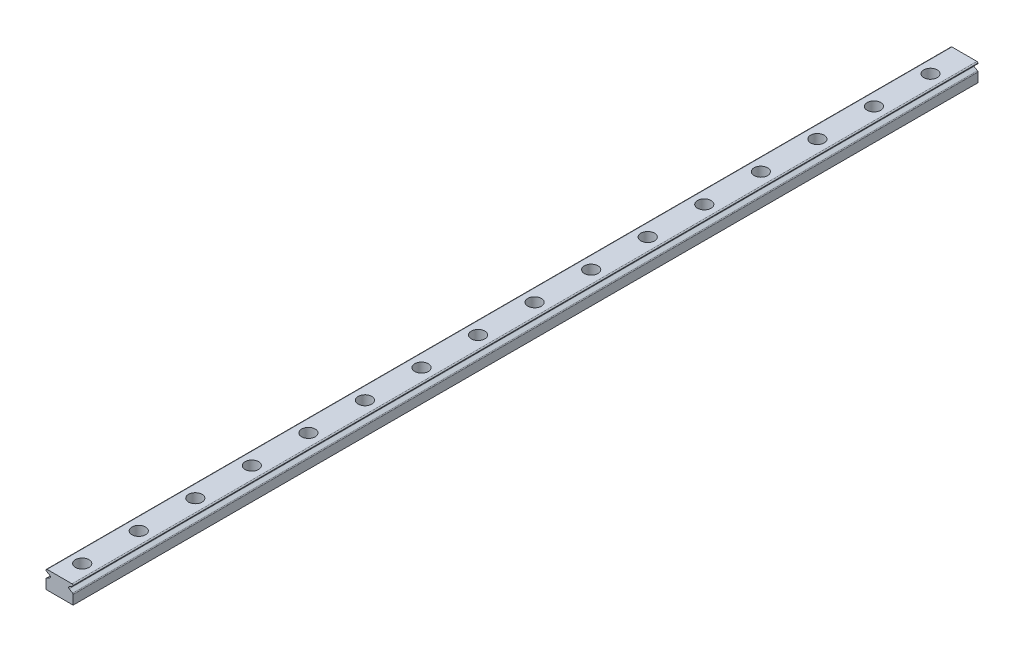
SolidWorks part; units mm, degrees
material "Plain Carbon Steel"
ref_plane "Front Plane" through (0, 0, 0) normal (0, 0, 1) x (1, 0, 0)
ref_plane "Top Plane" through (0, 0, 0) normal (0, 1, 0) x (1, 0, 0)
ref_plane "Right Plane" through (0, 0, 0) normal (1, 0, 0) x (0, 0, -1)
sketch "Sketch1" plane through (0, 0, 0) normal (0, 0, 1) x (1, 0, 0)
  line L4 (0, 0) -> (12, 0)
  line L5 (12, 0) -> (12, 8.4034)
  line L6 (12, 12) -> (0, 12)
  line L7 (0, 12) -> (0, 11.2902)
  line L8 (6, 12) -> (6, 7.6937) construction
  line L9 (6, 7.6937) -> (0, 7.6937) construction
  line L10 (0, 7.6937) -> (12, 7.6937) construction
  line L11 (6, 9.8468) -> (2.5, 9.8468) construction
  line L12 (6, 9.8468) -> (9.5, 9.8468) construction
  line L13 (9.5, 9.8468) -> (12, 11.2902)
  line L22 (9.5, 9.8468) -> (12, 8.4034)
  line L23 (2.5, 9.8468) -> (0, 11.2902)
  line L24 (2.5, 9.8468) -> (0, 8.4034)
  line L27 (12, 11.2902) -> (12, 12)
  line L28 (0, 8.4034) -> (0, 0)
  line L29 (7, 12) -> (7, 0) construction
  dimension "D3" = 3.5
  dimension "D1" = 6
  dimension "D2" = 7.6937
  dimension "D4" = 30
  dimension "D5" = 30
  dimension "D6" = 30
  dimension "D7" = 30
  dimension "D9" = 12
  dimension "D10" = 5
  dimension "D11" = 3.5
extrude "Boss-Extrude2" add sketch "Sketch1" along normal blind 400
fillet "Fillet5" radius 0.5 8 edges at (9.5, 9.8468, 200) (0, 12, 200) (12, 12, 200) (2.5, 9.8468, 200) (12, 8.4034, 200) (0, 8.4034, 200) (12, 11.2902, 200) (0, 11.2902, 200)
sketch "Sketch3" plane through (0, 12, 0) normal (0, 1, 0) x (1, 0, 0)
  line L0 (6, -400) -> (6, -490) construction
  line L1 (11.5, -400) -> (0.5, -400) construction
  line L2 (6, -490) -> (6, -440) construction
  line L3 (6, -440) -> (6, -465) construction
  circle A0 centre (6, -490) radius 3
  circle A1 centre (6, -440) radius 3
  circle A2 centre (6, -415) radius 3
  circle A3 centre (6, -390) radius 3
  circle A4 centre (6, -365) radius 3
  circle A5 centre (6, -340) radius 3
  circle A6 centre (6, -315) radius 3
  circle A7 centre (6, -290) radius 3
  circle A8 centre (6, -265) radius 3
  circle A9 centre (6, -240) radius 3
  circle A10 centre (6, -215) radius 3
  circle A11 centre (6, -190) radius 3
  circle A12 centre (6, -165) radius 3
  circle A13 centre (6, -140) radius 3
  circle A14 centre (6, -115) radius 3
  circle A15 centre (6, -90) radius 3
  circle A16 centre (6, -65) radius 3
  circle A17 centre (6, -40) radius 3
  circle A18 centre (6, -15) radius 3
  circle A19 centre (6, -465) radius 3
  dimension "D1" = 18
extrude "Cut-Extrude2" cut sketch "Sketch3" against normal blind 4.5
sketch "Sketch4" plane through (0, 12, 0) normal (0, 1, 0) x (1, 0, 0)
  line L0 (6, 0) -> (6, -15) construction
  line L1 (11.5, 0) -> (0.5, 0) construction
  circle A0 centre (6, -15) radius 1.75
  circle A1 centre (6, -40) radius 1.75
  circle A2 centre (6, -65) radius 1.75
  circle A3 centre (6, -90) radius 1.75
  circle A4 centre (6, -115) radius 1.75
  circle A5 centre (6, -140) radius 1.75
  circle A6 centre (6, -165) radius 1.75
  circle A7 centre (6, -190) radius 1.75
  circle A8 centre (6, -215) radius 1.75
  circle A9 centre (6, -240) radius 1.75
  circle A10 centre (6, -265) radius 1.75
  circle A11 centre (6, -290) radius 1.75
  circle A12 centre (6, -315) radius 1.75
  circle A13 centre (6, -340) radius 1.75
  circle A14 centre (6, -365) radius 1.75
  circle A15 centre (6, -390) radius 1.75
  circle A16 centre (6, -415) radius 1.75
  circle A17 centre (6, -440) radius 1.75
  circle A18 centre (6, -465) radius 1.75
  circle A19 centre (6, -490) radius 1.75
  dimension "D1" = 20
extrude "Cut-Extrude3" cut sketch "Sketch4" against normal blind 14.5
sketch "Sketch5" plane through (0, 0, 0) normal (0, 0, -1) x (-1, 0, 0)
  line L0 (-12, 0) -> (-12, 4.0574)
  line L2 (-12, 0) -> (-12, 8.1148) construction
  line L3 (-12, 4.0574) -> (0, 4.0574)
  line L4 (0, 8.1148) -> (0, 0) construction
  line L5 (0, 4.0574) -> (0, 0)
  line L6 (0, 0) -> (-12, 0)
extrude "Cut-Extrude4" cut sketch "Sketch5" against normal blind 682.5
